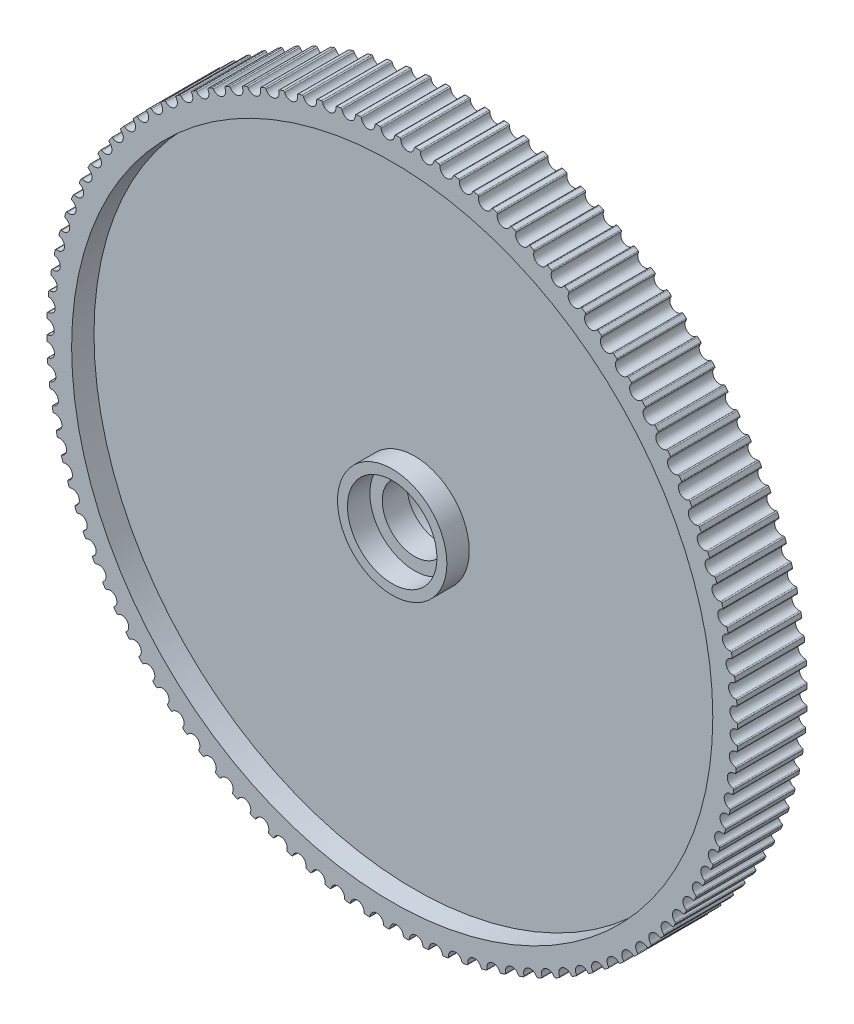
SolidWorks part; units mm, degrees
ref_plane "Front Plane" through (0, 0, 0) normal (0, 0, 1) x (1, 0, 0)
ref_plane "Top Plane" through (0, 0, 0) normal (0, 1, 0) x (1, 0, 0)
ref_plane "Right Plane" through (0, 0, 0) normal (1, 0, 0) x (0, 0, -1)
sketch "Sketch2" plane through (0, 0, 0) normal (0, 0, 1) x (1, 0, 0)
  circle A0 centre (0, 0) radius 35.03 construction
  arc A1 (-3.2113, 34.6013) -> (-3.0921, 34.5062) centre (-3.2012, 34.4918) cw
  arc A2 (-3.0921, 34.5062) -> (-1.738, 34.6009) centre (-2.418, 34.5956) ccw
  arc A3 (-1.738, 34.6009) -> (-1.6332, 34.7116) centre (-1.628, 34.6017) cw
  arc A4 (-1.6332, 34.7116) -> (-1.2307, 34.7282) centre (0, 0) cw
  circle A5 centre (0, 0) radius 34.75 construction
  circle A6 centre (0, 0) radius 34 construction
  arc A7 (0.3511, 34.7482) -> (0.7538, 34.7418) centre (0, 0) cw
  arc A8 (0.2401, 34.6437) -> (0.3511, 34.7482) centre (0.35, 34.6382) cw
  arc A9 (-1.1172, 34.6265) -> (0.2401, 34.6437) centre (-0.4391, 34.6772) ccw
  arc A10 (-1.2307, 34.7282) -> (-1.1172, 34.6265) centre (-1.2269, 34.6183) cw
  arc A11 (2.3343, 34.6715) -> (2.736, 34.6421) centre (0, 0) cw
  arc A12 (2.2175, 34.5735) -> (2.3343, 34.6715) centre (2.3269, 34.5618) cw
  arc A13 (0.8614, 34.6338) -> (2.2175, 34.5735) centre (1.5413, 34.6457) ccw
  arc A14 (0.7538, 34.7418) -> (0.8614, 34.6338) centre (0.7515, 34.6318) cw
  arc A15 (4.3098, 34.4817) -> (4.7092, 34.4294) centre (0, 0) cw
  arc A16 (4.1876, 34.3905) -> (4.3098, 34.4817) centre (4.2962, 34.3726) cw
  arc A17 (2.8372, 34.5281) -> (4.1876, 34.3905) centre (3.5167, 34.5012) ccw
  arc A18 (2.736, 34.6421) -> (2.8372, 34.5281) centre (2.7273, 34.5325) cw
  arc A19 (6.2713, 34.1794) -> (6.6671, 34.1044) centre (0, 0) cw
  arc A20 (6.1441, 34.0953) -> (6.2713, 34.1794) centre (6.2514, 34.0712) cw
  arc A21 (4.8038, 34.3098) -> (6.1441, 34.0953) centre (5.4806, 34.2442) ccw
  arc A22 (4.7092, 34.4294) -> (4.8038, 34.3098) centre (4.6943, 34.3204) cw
  arc A23 (8.2123, 33.7657) -> (8.6032, 33.6682) centre (0, 0) cw
  arc A24 (8.0806, 33.689) -> (8.2123, 33.7657) centre (8.1863, 33.6588) cw
  arc A25 (6.7547, 33.9796) -> (8.0806, 33.689) centre (7.4266, 33.8755) ccw
  arc A26 (6.6671, 34.1044) -> (6.7547, 33.9796) centre (6.646, 33.9965) cw
  arc A27 (10.1266, 33.2418) -> (10.5112, 33.1222) centre (0, 0) cw
  arc A28 (9.9906, 33.1727) -> (10.1266, 33.2418) centre (10.0945, 33.1365) cw
  arc A29 (8.6835, 33.5386) -> (9.9906, 33.1727) centre (9.3484, 33.3962) ccw
  arc A30 (8.6032, 33.6682) -> (8.6835, 33.5386) centre (8.5759, 33.5616) cw
  arc A31 (12.0078, 32.6094) -> (12.385, 32.4681) centre (0, 0) cw
  arc A32 (11.8681, 32.5482) -> (12.0078, 32.6094) centre (11.9698, 32.5062) cw
  arc A33 (10.584, 32.9882) -> (11.8681, 32.5482) centre (11.2397, 32.8081) ccw
  arc A34 (10.5112, 33.1222) -> (10.584, 32.9882) centre (10.4779, 33.0173) cw
  arc A35 (13.8498, 31.8707) -> (14.2183, 31.7081) centre (0, 0) cw
  arc A36 (13.7069, 31.8176) -> (13.8498, 31.8707) centre (13.806, 31.7699) cw
  arc A37 (12.45, 32.3301) -> (13.7069, 31.8176) centre (13.0944, 32.1129) ccw
  arc A38 (12.385, 32.4681) -> (12.45, 32.3301) centre (12.3458, 32.3653) cw
  arc A39 (15.6467, 31.0281) -> (16.0053, 30.8446) centre (0, 0) cw
  arc A40 (15.501, 30.9832) -> (15.6467, 31.0281) centre (15.5972, 30.9299) cw
  arc A41 (14.2754, 31.5667) -> (15.501, 30.9832) centre (14.9063, 31.313) ccw
  arc A42 (14.2183, 31.7081) -> (14.2754, 31.5667) centre (14.1733, 31.6077) cw
  arc A43 (17.3926, 30.0842) -> (17.7401, 29.8806) centre (0, 0) cw
  arc A44 (17.2445, 30.0478) -> (17.3926, 30.0842) centre (17.3375, 29.989) cw
  arc A45 (16.0542, 30.7002) -> (17.2445, 30.0478) centre (16.6696, 30.411) ccw
  arc A46 (16.0053, 30.8446) -> (16.0542, 30.7002) centre (15.9547, 30.747) cw
  arc A47 (19.0817, 29.0423) -> (19.417, 28.8191) centre (0, 0) cw
  arc A48 (18.9318, 29.0143) -> (19.0817, 29.0423) centre (19.0213, 28.9503) cw
  arc A49 (17.7807, 29.7336) -> (18.9318, 29.0143) centre (18.3786, 29.4097) ccw
  arc A50 (17.7401, 29.8806) -> (17.7807, 29.7336) centre (17.684, 29.786) cw
  arc A51 (20.7085, 27.9055) -> (21.0306, 27.6636) centre (0, 0) cw
  arc A52 (20.5573, 27.8862) -> (20.7085, 27.9055) centre (20.643, 27.8172) cw
  arc A53 (19.4491, 28.6701) -> (20.5573, 27.8862) centre (20.0276, 28.3125) ccw
  arc A54 (19.417, 28.8191) -> (19.4491, 28.6701) centre (19.3556, 28.7279) cw
  arc A55 (22.2679, 26.6778) -> (22.5756, 26.4179) centre (0, 0) cw
  arc A56 (22.1158, 26.6671) -> (22.2679, 26.6778) centre (22.1974, 26.5934) cw
  arc A57 (21.0542, 27.513) -> (22.1158, 26.6671) centre (21.6112, 27.123) ccw
  arc A58 (21.0306, 27.6636) -> (21.0542, 27.513) centre (20.964, 27.5761) cw
  arc A59 (23.7545, 25.363) -> (24.0469, 25.086) centre (0, 0) cw
  arc A60 (23.6021, 25.361) -> (23.7545, 25.363) centre (23.6793, 25.2828) cw
  arc A61 (22.5905, 26.2661) -> (23.6021, 25.361) centre (23.1244, 25.845) ccw
  arc A62 (22.5756, 26.4179) -> (22.5905, 26.2661) centre (22.5041, 26.3343) cw
  arc A63 (25.1637, 23.9656) -> (25.4399, 23.6723) centre (0, 0) cw
  arc A64 (25.0114, 23.9723) -> (25.1637, 23.9656) centre (25.0841, 23.8897) cw
  arc A65 (24.0532, 24.9336) -> (25.0114, 23.9723) centre (24.5621, 24.4827) ccw
  arc A66 (24.0469, 25.086) -> (24.0532, 24.9336) centre (23.9708, 25.0066) cw
  arc A67 (26.4909, 22.4899) -> (26.7498, 22.1813) centre (0, 0) cw
  arc A68 (26.3392, 22.5053) -> (26.4909, 22.4899) centre (26.407, 22.4187) cw
  arc A69 (25.4374, 23.5198) -> (26.3392, 22.5053) centre (25.9198, 23.0406) ccw
  arc A70 (25.4399, 23.6723) -> (25.4374, 23.5198) centre (25.3593, 23.5973) cw
  arc A71 (27.7316, 20.9409) -> (27.9725, 20.618) centre (0, 0) cw
  arc A72 (27.581, 20.9649) -> (27.7316, 20.9409) centre (27.6438, 20.8746) cw
  arc A73 (26.7386, 22.0293) -> (27.581, 20.9649) centre (27.1929, 21.5233) ccw
  arc A74 (26.7498, 22.1813) -> (26.7386, 22.0293) centre (26.6651, 22.1111) cw
  arc A75 (28.8819, 19.3236) -> (29.1039, 18.9875) centre (0, 0) cw
  arc A76 (28.7329, 19.3562) -> (28.8819, 19.3236) centre (28.7904, 19.2624) cw
  arc A77 (27.9526, 20.4669) -> (28.7329, 19.3562) centre (28.3772, 19.9358) ccw
  arc A78 (27.9725, 20.618) -> (27.9526, 20.4669) centre (27.8839, 20.5528) cw
  arc A79 (29.9379, 17.6432) -> (30.1404, 17.295) centre (0, 0) cw
  arc A80 (29.7911, 17.6843) -> (29.9379, 17.6432) centre (29.8431, 17.5874) cw
  arc A81 (29.0755, 18.8377) -> (29.7911, 17.6843) centre (29.4691, 18.2832) ccw
  arc A82 (29.1039, 18.9875) -> (29.0755, 18.8377) centre (29.0118, 18.9274) cw
  arc A83 (30.8963, 15.9053) -> (31.0786, 15.5461) centre (0, 0) cw
  arc A84 (30.752, 15.9547) -> (30.8963, 15.9053) centre (30.7985, 15.855) cw
  arc A85 (30.1035, 17.1471) -> (30.752, 15.9547) centre (30.4648, 16.571) ccw
  arc A86 (30.1404, 17.295) -> (30.1035, 17.1471) centre (30.045, 17.2403) cw
  arc A87 (31.7539, 14.1156) -> (31.9154, 13.7465) centre (0, 0) cw
  arc A88 (31.6127, 14.1731) -> (31.7539, 14.1156) centre (31.6534, 14.0709) cw
  arc A89 (31.0333, 15.4006) -> (31.6127, 14.1731) centre (31.3611, 14.8048) ccw
  arc A90 (31.0786, 15.5461) -> (31.0333, 15.4006) centre (30.9802, 15.4969) cw
  arc A91 (32.508, 12.2798) -> (32.6482, 11.9021) centre (0, 0) cw
  arc A92 (32.3703, 12.3452) -> (32.508, 12.2798) centre (32.4051, 12.2409) cw
  arc A93 (31.8619, 13.6038) -> (32.3703, 12.3452) centre (32.1552, 12.9903) ccw
  arc A94 (31.9154, 13.7465) -> (31.8619, 13.6038) centre (31.8144, 13.703) cw
  arc A95 (33.156, 10.4039) -> (33.2744, 10.0189) centre (0, 0) cw
  arc A96 (33.0223, 10.4771) -> (33.156, 10.4039) centre (33.0511, 10.371) cw
  arc A97 (32.5865, 11.7627) -> (33.0223, 10.4771) centre (32.8443, 11.1334) ccw
  arc A98 (32.6482, 11.9021) -> (32.5865, 11.7627) centre (32.5448, 11.8644) cw
  arc A99 (33.6959, 8.4941) -> (33.7921, 8.1029) centre (0, 0) cw
  arc A100 (33.5665, 8.5748) -> (33.6959, 8.4941) centre (33.5892, 8.4672) cw
  arc A101 (33.2049, 9.8831) -> (33.5665, 8.5748) centre (33.4263, 9.2402) ccw
  arc A102 (33.2744, 10.0189) -> (33.2049, 9.8831) centre (33.1691, 9.9871) cw
  arc A103 (34.1259, 6.5566) -> (34.1996, 6.1606) centre (0, 0) cw
  arc A104 (34.0013, 6.6446) -> (34.1259, 6.5566) centre (34.0178, 6.5358) cw
  arc A105 (33.7149, 7.9714) -> (34.0013, 6.6446) centre (33.8993, 7.3169) ccw
  arc A106 (33.7921, 8.1029) -> (33.7149, 7.9714) centre (33.6851, 8.0773) cw
  arc A107 (34.4445, 4.5977) -> (34.4955, 4.1981) centre (0, 0) cw
  arc A108 (34.3252, 4.6926) -> (34.4445, 4.5977) centre (34.3355, 4.5831) cw
  arc A109 (34.115, 6.0337) -> (34.3252, 4.6926) centre (34.2618, 5.3697) ccw
  arc A110 (34.1996, 6.1606) -> (34.115, 6.0337) centre (34.0913, 6.1411) cw
  arc A111 (34.6508, 2.6238) -> (34.6789, 2.2219) centre (0, 0) cw
  arc A112 (34.5371, 2.7254) -> (34.6508, 2.6238) centre (34.5411, 2.6155) cw
  arc A113 (34.4039, 4.0762) -> (34.5371, 2.7254) centre (34.5124, 3.4049) ccw
  arc A114 (34.4955, 4.1981) -> (34.4039, 4.0762) centre (34.3863, 4.1848) cw
  arc A115 (34.7441, 0.6413) -> (34.7492, 0.2385) centre (0, 0) cw
  arc A116 (34.6364, 0.7493) -> (34.7441, 0.6413) centre (34.6341, 0.6393) cw
  arc A117 (34.5805, 2.1055) -> (34.6364, 0.7493) centre (34.6505, 1.4291) ccw
  arc A118 (34.6789, 2.2219) -> (34.5805, 2.1055) centre (34.5691, 2.2149) cw
  arc A119 (34.724, -1.3432) -> (34.7061, -1.7456) centre (0, 0) cw
  arc A120 (34.6227, -1.2293) -> (34.724, -1.3432) centre (34.6141, -1.339) cw
  arc A121 (34.6443, 0.1279) -> (34.6227, -1.2293) centre (34.6756, -0.5514) ccw
  arc A122 (34.7492, 0.2385) -> (34.6443, 0.1279) centre (34.6392, 0.2378) cw
  arc A123 (34.5907, -3.3234) -> (34.5499, -3.7241) centre (0, 0) cw
  arc A124 (34.496, -3.2039) -> (34.5907, -3.3234) centre (34.4812, -3.3129) cw
  arc A125 (34.5951, -1.8501) -> (34.496, -3.2039) centre (34.5876, -2.5301) ccw
  arc A126 (34.7061, -1.7456) -> (34.5951, -1.8501) centre (34.5963, -1.7401) cw
  arc A127 (34.3446, -5.2927) -> (34.2809, -5.6905) centre (0, 0) cw
  arc A128 (34.2569, -5.168) -> (34.3446, -5.2927) centre (34.2359, -5.276) cw
  arc A129 (34.433, -3.8221) -> (34.2569, -5.168) centre (34.3867, -4.5005) ccw
  arc A130 (34.5499, -3.7241) -> (34.433, -3.8221) centre (34.4405, -3.7123) cw
  arc A131 (33.9864, -7.2448) -> (33.9001, -7.6382) centre (0, 0) cw
  arc A132 (33.906, -7.1152) -> (33.9864, -7.2448) centre (33.8788, -7.2218) cw
  arc A133 (34.1587, -5.7816) -> (33.906, -7.1152) centre (34.0737, -6.4563) ccw
  arc A134 (34.2809, -5.6905) -> (34.1587, -5.7816) centre (34.1724, -5.6724) cw
  arc A135 (33.5174, -9.1732) -> (33.4088, -9.5611) centre (0, 0) cw
  arc A136 (33.4445, -9.0393) -> (33.5174, -9.1732) centre (33.4113, -9.1442) cw
  arc A137 (33.7729, -7.7222) -> (33.4445, -9.0393) centre (33.6496, -8.391) ccw
  arc A138 (33.9001, -7.6382) -> (33.7729, -7.7222) centre (33.7928, -7.6141) cw
  arc A139 (32.939, -11.0717) -> (32.8085, -11.4528) centre (0, 0) cw
  arc A140 (32.8739, -10.9338) -> (32.939, -11.0717) centre (32.8348, -11.0367) cw
  arc A141 (33.277, -9.6377) -> (32.8739, -10.9338) centre (33.1157, -10.2983) ccw
  arc A142 (33.4088, -9.5611) -> (33.277, -9.6377) centre (33.303, -9.5308) cw
  arc A143 (32.2532, -12.9341) -> (32.1012, -13.3071) centre (0, 0) cw
  arc A144 (32.1961, -12.7927) -> (32.2532, -12.9341) centre (32.1511, -12.8932) cw
  arc A145 (32.6725, -11.5217) -> (32.1961, -12.7927) centre (32.4737, -12.172) ccw
  arc A146 (32.8085, -11.4528) -> (32.6725, -11.5217) centre (32.7046, -11.4165) cw
  arc A147 (31.4622, -14.7543) -> (31.2891, -15.118) centre (0, 0) cw
  arc A148 (31.4132, -14.6099) -> (31.4622, -14.7543) centre (31.3627, -14.7076) cw
  arc A149 (31.9614, -13.3682) -> (31.4132, -14.6099) centre (31.7259, -14.0061) ccw
  arc A150 (32.1012, -13.3071) -> (31.9614, -13.3682) centre (31.9995, -13.265) cw
  arc A151 (30.5686, -16.5264) -> (30.375, -16.8796) centre (0, 0) cw
  arc A152 (30.5279, -16.3794) -> (30.5686, -16.5264) centre (30.4719, -16.4741) cw
  arc A153 (31.1461, -15.171) -> (30.5279, -16.3794) centre (30.8746, -15.7944) ccw
  arc A154 (31.2891, -15.118) -> (31.1461, -15.171) centre (31.1901, -15.0701) cw
  arc A155 (29.5753, -18.2446) -> (29.3618, -18.5861) centre (0, 0) cw
  arc A156 (29.5431, -18.0955) -> (29.5753, -18.2446) centre (29.4817, -18.1868) cw
  arc A157 (30.2292, -16.9243) -> (29.5431, -18.0955) centre (29.9225, -17.5312) ccw
  arc A158 (30.375, -16.8796) -> (30.2292, -16.9243) centre (30.2789, -16.8262) cw
  arc A159 (28.4855, -19.9032) -> (28.2529, -20.2321) centre (0, 0) cw
  arc A160 (28.4618, -19.7526) -> (28.4855, -19.9032) centre (28.3953, -19.8402) cw
  arc A161 (29.2138, -18.6225) -> (28.4618, -19.7526) centre (28.8729, -19.2109) ccw
  arc A162 (29.3618, -18.5861) -> (29.2138, -18.6225) centre (29.2689, -18.5273) cw
  arc A163 (27.3028, -21.497) -> (27.0518, -21.812) centre (0, 0) cw
  arc A164 (27.2878, -21.3452) -> (27.3028, -21.497) centre (27.2164, -21.4289) cw
  arc A165 (28.103, -20.2599) -> (27.2878, -21.3452) centre (27.7291, -20.8279) ccw
  arc A166 (28.2529, -20.2321) -> (28.103, -20.2599) centre (28.1635, -20.168) cw
  arc A167 (26.031, -23.0206) -> (25.7625, -23.3208) centre (0, 0) cw
  arc A168 (26.0247, -22.8682) -> (26.031, -23.0206) centre (25.9486, -22.9477) cw
  arc A169 (26.9005, -21.8312) -> (26.0247, -22.8682) centre (26.4948, -22.3769) ccw
  arc A170 (27.0518, -21.812) -> (26.9005, -21.8312) centre (26.9662, -21.743) cw
  arc A171 (24.6744, -24.4691) -> (24.3891, -24.7535) centre (0, 0) cw
  arc A172 (24.6767, -24.3167) -> (24.6744, -24.4691) centre (24.5963, -24.3917) cw
  arc A173 (25.6103, -23.3313) -> (24.6767, -24.3167) centre (25.1741, -23.853) ccw
  arc A174 (25.7625, -23.3208) -> (25.6103, -23.3313) centre (25.6809, -23.247) cw
  arc A175 (23.2372, -25.8378) -> (22.9362, -26.1055) centre (0, 0) cw
  arc A176 (23.2483, -25.6858) -> (23.2372, -25.8378) centre (23.1637, -25.7561) cw
  arc A177 (24.2366, -24.7554) -> (23.2483, -25.6858) centre (23.7713, -25.2513) ccw
  arc A178 (24.3891, -24.7535) -> (24.2366, -24.7554) centre (24.3119, -24.6751) cw
  arc A179 (21.7243, -27.1223) -> (21.4084, -27.3723) centre (0, 0) cw
  arc A180 (21.744, -26.9711) -> (21.7243, -27.1223) centre (21.6555, -27.0364) cw
  arc A181 (22.7838, -26.0986) -> (21.744, -26.9711) centre (22.291, -26.5672) ccw
  arc A182 (22.9362, -26.1055) -> (22.7838, -26.0986) centre (22.8636, -26.0228) cw
  arc A183 (20.1405, -28.3183) -> (19.8109, -28.5498) centre (0, 0) cw
  arc A184 (20.1688, -28.1684) -> (20.1405, -28.3183) centre (20.0767, -28.2286) cw
  arc A185 (21.2567, -27.3568) -> (20.1688, -28.1684) centre (20.738, -27.7964) ccw
  arc A186 (21.4084, -27.3723) -> (21.2567, -27.3568) centre (21.3407, -27.2856) cw
  arc A187 (18.491, -29.4219) -> (18.1487, -29.6342) centre (0, 0) cw
  arc A188 (18.5278, -29.2739) -> (18.491, -29.4219) centre (18.4324, -29.3287) cw
  arc A189 (19.6603, -28.5257) -> (18.5278, -29.2739) centre (19.1173, -28.935) ccw
  arc A190 (19.8109, -28.5498) -> (19.6603, -28.5257) centre (19.7481, -28.4595) cw
  arc A191 (16.7811, -30.4295) -> (16.4273, -30.622) centre (0, 0) cw
  arc A192 (16.8263, -30.2839) -> (16.7811, -30.4295) centre (16.728, -30.3332) cw
  arc A193 (17.9997, -29.6015) -> (16.8263, -30.2839) centre (17.4342, -29.9792) ccw
  arc A194 (18.1487, -29.6342) -> (17.9997, -29.6015) centre (18.0912, -29.5404) cw
  arc A195 (15.0166, -31.3379) -> (14.6523, -31.5099) centre (0, 0) cw
  arc A196 (15.07, -31.1951) -> (15.0166, -31.3379) centre (14.969, -31.2387) cw
  arc A197 (16.2805, -30.5808) -> (15.07, -31.1951) centre (15.6943, -30.9256) ccw
  arc A198 (16.4273, -30.622) -> (16.2805, -30.5808) centre (16.3753, -30.5251) cw
  arc A199 (13.203, -32.1441) -> (12.8296, -32.295) centre (0, 0) cw
  arc A200 (13.2646, -32.0046) -> (13.203, -32.1441) centre (13.1613, -32.0423) cw
  arc A201 (14.5081, -31.4604) -> (13.2646, -32.0046) centre (13.9032, -31.7711) ccw
  arc A202 (14.6523, -31.5099) -> (14.5081, -31.4604) centre (14.6059, -31.4101) cw
  arc A203 (11.3464, -32.8454) -> (10.965, -32.9747) centre (0, 0) cw
  arc A204 (11.4158, -32.7096) -> (11.3464, -32.8454) centre (11.3105, -32.7414) cw
  arc A205 (12.6884, -32.2373) -> (11.4158, -32.7096) centre (12.0668, -32.513) ccw
  arc A206 (12.8296, -32.295) -> (12.6884, -32.2373) centre (12.789, -32.1927) cw
  arc A207 (9.4528, -33.4396) -> (9.0646, -33.5469) centre (0, 0) cw
  arc A208 (9.5299, -33.308) -> (9.4528, -33.4396) centre (9.4229, -33.3337) cw
  arc A209 (10.8273, -32.9091) -> (9.5299, -33.308) centre (10.191, -33.1489) ccw
  arc A210 (10.965, -32.9747) -> (10.8273, -32.9091) centre (10.9302, -32.8703) cw
  arc A211 (7.5284, -33.9247) -> (7.1347, -34.0097) centre (0, 0) cw
  arc A212 (7.6128, -33.7977) -> (7.5284, -33.9247) centre (7.5046, -33.8173) cw
  arc A213 (8.9309, -33.4736) -> (7.6128, -33.7977) centre (8.2819, -33.6766) ccw
  arc A214 (9.0646, -33.5469) -> (8.9309, -33.4736) centre (9.0359, -33.4407) cw
  arc A215 (5.5794, -34.2992) -> (5.1814, -34.3615) centre (0, 0) cw
  arc A216 (5.6709, -34.1772) -> (5.5794, -34.2992) centre (5.5617, -34.1906) cw
  arc A217 (7.0054, -33.9288) -> (5.6709, -34.1772) centre (6.3459, -34.0945) ccw
  arc A218 (7.1347, -34.0097) -> (7.0054, -33.9288) centre (7.1121, -33.902) cw
  arc A219 (3.6122, -34.5617) -> (3.2113, -34.6013) centre (0, 0) cw
  arc A220 (3.7105, -34.4452) -> (3.6122, -34.5617) centre (3.6008, -34.4523) cw
  arc A221 (5.057, -34.2734) -> (3.7105, -34.4452) centre (4.3891, -34.4011) ccw
  arc A222 (5.1814, -34.3615) -> (5.057, -34.2734) centre (5.165, -34.2528) cw
  arc A223 (1.6332, -34.7116) -> (1.2307, -34.7282) centre (0, 0) cw
  arc A224 (1.738, -34.6009) -> (1.6332, -34.7116) centre (1.628, -34.6017) cw
  arc A225 (3.0921, -34.5062) -> (1.738, -34.6009) centre (2.418, -34.5956) ccw
  arc A226 (3.2113, -34.6013) -> (3.0921, -34.5062) centre (3.2012, -34.4918) cw
  arc A227 (-0.3511, -34.7482) -> (-0.7538, -34.7418) centre (0, 0) cw
  arc A228 (-0.2401, -34.6437) -> (-0.3511, -34.7482) centre (-0.35, -34.6382) cw
  arc A229 (1.1172, -34.6265) -> (-0.2401, -34.6437) centre (0.4391, -34.6772) ccw
  arc A230 (1.2307, -34.7282) -> (1.1172, -34.6265) centre (1.2269, -34.6183) cw
  arc A231 (-2.3343, -34.6715) -> (-2.736, -34.6421) centre (0, 0) cw
  arc A232 (-2.2175, -34.5735) -> (-2.3343, -34.6715) centre (-2.3269, -34.5618) cw
  arc A233 (-0.8614, -34.6338) -> (-2.2175, -34.5735) centre (-1.5413, -34.6457) ccw
  arc A234 (-0.7538, -34.7418) -> (-0.8614, -34.6338) centre (-0.7515, -34.6318) cw
  arc A235 (-4.3098, -34.4817) -> (-4.7092, -34.4294) centre (0, 0) cw
  arc A236 (-4.1876, -34.3905) -> (-4.3098, -34.4817) centre (-4.2962, -34.3726) cw
  arc A237 (-2.8372, -34.5281) -> (-4.1876, -34.3905) centre (-3.5167, -34.5012) ccw
  arc A238 (-2.736, -34.6421) -> (-2.8372, -34.5281) centre (-2.7273, -34.5325) cw
  arc A239 (-6.2713, -34.1794) -> (-6.6671, -34.1044) centre (0, 0) cw
  arc A240 (-6.1441, -34.0953) -> (-6.2713, -34.1794) centre (-6.2514, -34.0712) cw
  arc A241 (-4.8038, -34.3098) -> (-6.1441, -34.0953) centre (-5.4806, -34.2442) ccw
  arc A242 (-4.7092, -34.4294) -> (-4.8038, -34.3098) centre (-4.6943, -34.3204) cw
  arc A243 (-8.2123, -33.7657) -> (-8.6032, -33.6682) centre (0, 0) cw
  arc A244 (-8.0806, -33.689) -> (-8.2123, -33.7657) centre (-8.1863, -33.6588) cw
  arc A245 (-6.7547, -33.9796) -> (-8.0806, -33.689) centre (-7.4266, -33.8755) ccw
  arc A246 (-6.6671, -34.1044) -> (-6.7547, -33.9796) centre (-6.646, -33.9965) cw
  arc A247 (-10.1266, -33.2418) -> (-10.5112, -33.1222) centre (0, 0) cw
  arc A248 (-9.9906, -33.1727) -> (-10.1266, -33.2418) centre (-10.0945, -33.1365) cw
  arc A249 (-8.6835, -33.5386) -> (-9.9906, -33.1727) centre (-9.3484, -33.3962) ccw
  arc A250 (-8.6032, -33.6682) -> (-8.6835, -33.5386) centre (-8.5759, -33.5616) cw
  arc A251 (-12.0078, -32.6094) -> (-12.385, -32.4681) centre (0, 0) cw
  arc A252 (-11.8681, -32.5482) -> (-12.0078, -32.6094) centre (-11.9698, -32.5062) cw
  arc A253 (-10.584, -32.9882) -> (-11.8681, -32.5482) centre (-11.2397, -32.8081) ccw
  arc A254 (-10.5112, -33.1222) -> (-10.584, -32.9882) centre (-10.4779, -33.0173) cw
  arc A255 (-13.8498, -31.8707) -> (-14.2183, -31.7081) centre (0, 0) cw
  arc A256 (-13.7069, -31.8176) -> (-13.8498, -31.8707) centre (-13.806, -31.7699) cw
  arc A257 (-12.45, -32.3301) -> (-13.7069, -31.8176) centre (-13.0944, -32.1129) ccw
  arc A258 (-12.385, -32.4681) -> (-12.45, -32.3301) centre (-12.3458, -32.3653) cw
  arc A259 (-15.6467, -31.0281) -> (-16.0053, -30.8446) centre (0, 0) cw
  arc A260 (-15.501, -30.9832) -> (-15.6467, -31.0281) centre (-15.5972, -30.9299) cw
  arc A261 (-14.2754, -31.5667) -> (-15.501, -30.9832) centre (-14.9063, -31.313) ccw
  arc A262 (-14.2183, -31.7081) -> (-14.2754, -31.5667) centre (-14.1733, -31.6077) cw
  arc A263 (-17.3926, -30.0842) -> (-17.7401, -29.8806) centre (0, 0) cw
  arc A264 (-17.2445, -30.0478) -> (-17.3926, -30.0842) centre (-17.3375, -29.989) cw
  arc A265 (-16.0542, -30.7002) -> (-17.2445, -30.0478) centre (-16.6696, -30.411) ccw
  arc A266 (-16.0053, -30.8446) -> (-16.0542, -30.7002) centre (-15.9547, -30.747) cw
  arc A267 (-19.0817, -29.0423) -> (-19.417, -28.8191) centre (0, 0) cw
  arc A268 (-18.9318, -29.0143) -> (-19.0817, -29.0423) centre (-19.0213, -28.9503) cw
  arc A269 (-17.7807, -29.7336) -> (-18.9318, -29.0143) centre (-18.3786, -29.4097) ccw
  arc A270 (-17.7401, -29.8806) -> (-17.7807, -29.7336) centre (-17.684, -29.786) cw
  arc A271 (-20.7085, -27.9055) -> (-21.0306, -27.6636) centre (0, 0) cw
  arc A272 (-20.5573, -27.8862) -> (-20.7085, -27.9055) centre (-20.643, -27.8172) cw
  arc A273 (-19.4491, -28.6701) -> (-20.5573, -27.8862) centre (-20.0276, -28.3125) ccw
  arc A274 (-19.417, -28.8191) -> (-19.4491, -28.6701) centre (-19.3556, -28.7279) cw
  arc A275 (-22.2679, -26.6778) -> (-22.5756, -26.4179) centre (0, 0) cw
  arc A276 (-22.1158, -26.6671) -> (-22.2679, -26.6778) centre (-22.1974, -26.5934) cw
  arc A277 (-21.0542, -27.513) -> (-22.1158, -26.6671) centre (-21.6112, -27.123) ccw
  arc A278 (-21.0306, -27.6636) -> (-21.0542, -27.513) centre (-20.964, -27.5761) cw
  arc A279 (-23.7545, -25.363) -> (-24.0469, -25.086) centre (0, 0) cw
  arc A280 (-23.6021, -25.361) -> (-23.7545, -25.363) centre (-23.6793, -25.2828) cw
  arc A281 (-22.5905, -26.2661) -> (-23.6021, -25.361) centre (-23.1244, -25.845) ccw
  arc A282 (-22.5756, -26.4179) -> (-22.5905, -26.2661) centre (-22.5041, -26.3343) cw
  arc A283 (-25.1637, -23.9656) -> (-25.4399, -23.6723) centre (0, 0) cw
  arc A284 (-25.0114, -23.9723) -> (-25.1637, -23.9656) centre (-25.0841, -23.8897) cw
  arc A285 (-24.0532, -24.9336) -> (-25.0114, -23.9723) centre (-24.5621, -24.4827) ccw
  arc A286 (-24.0469, -25.086) -> (-24.0532, -24.9336) centre (-23.9708, -25.0066) cw
  arc A287 (-26.4909, -22.4899) -> (-26.7498, -22.1813) centre (0, 0) cw
  arc A288 (-26.3392, -22.5053) -> (-26.4909, -22.4899) centre (-26.407, -22.4187) cw
  arc A289 (-25.4374, -23.5198) -> (-26.3392, -22.5053) centre (-25.9198, -23.0406) ccw
  arc A290 (-25.4399, -23.6723) -> (-25.4374, -23.5198) centre (-25.3593, -23.5973) cw
  arc A291 (-27.7316, -20.9409) -> (-27.9725, -20.618) centre (0, 0) cw
  arc A292 (-27.581, -20.9649) -> (-27.7316, -20.9409) centre (-27.6438, -20.8746) cw
  arc A293 (-26.7386, -22.0293) -> (-27.581, -20.9649) centre (-27.1929, -21.5233) ccw
  arc A294 (-26.7498, -22.1813) -> (-26.7386, -22.0293) centre (-26.6651, -22.1111) cw
  arc A295 (-28.8819, -19.3236) -> (-29.1039, -18.9875) centre (0, 0) cw
  arc A296 (-28.7329, -19.3562) -> (-28.8819, -19.3236) centre (-28.7904, -19.2624) cw
  arc A297 (-27.9526, -20.4669) -> (-28.7329, -19.3562) centre (-28.3772, -19.9358) ccw
  arc A298 (-27.9725, -20.618) -> (-27.9526, -20.4669) centre (-27.8839, -20.5528) cw
  arc A299 (-29.9379, -17.6432) -> (-30.1404, -17.295) centre (0, 0) cw
  arc A300 (-29.7911, -17.6843) -> (-29.9379, -17.6432) centre (-29.8431, -17.5874) cw
  arc A301 (-29.0755, -18.8377) -> (-29.7911, -17.6843) centre (-29.4691, -18.2832) ccw
  arc A302 (-29.1039, -18.9875) -> (-29.0755, -18.8377) centre (-29.0118, -18.9274) cw
  arc A303 (-30.8963, -15.9053) -> (-31.0786, -15.5461) centre (0, 0) cw
  arc A304 (-30.752, -15.9547) -> (-30.8963, -15.9053) centre (-30.7985, -15.855) cw
  arc A305 (-30.1035, -17.1471) -> (-30.752, -15.9547) centre (-30.4648, -16.571) ccw
  arc A306 (-30.1404, -17.295) -> (-30.1035, -17.1471) centre (-30.045, -17.2403) cw
  arc A307 (-31.7539, -14.1156) -> (-31.9154, -13.7465) centre (0, 0) cw
  arc A308 (-31.6127, -14.1731) -> (-31.7539, -14.1156) centre (-31.6534, -14.0709) cw
  arc A309 (-31.0333, -15.4006) -> (-31.6127, -14.1731) centre (-31.3611, -14.8048) ccw
  arc A310 (-31.0786, -15.5461) -> (-31.0333, -15.4006) centre (-30.9802, -15.4969) cw
  arc A311 (-32.508, -12.2798) -> (-32.6482, -11.9021) centre (0, 0) cw
  arc A312 (-32.3703, -12.3452) -> (-32.508, -12.2798) centre (-32.4051, -12.2409) cw
  arc A313 (-31.8619, -13.6038) -> (-32.3703, -12.3452) centre (-32.1552, -12.9903) ccw
  arc A314 (-31.9154, -13.7465) -> (-31.8619, -13.6038) centre (-31.8144, -13.703) cw
  arc A315 (-33.156, -10.4039) -> (-33.2744, -10.0189) centre (0, 0) cw
  arc A316 (-33.0223, -10.4771) -> (-33.156, -10.4039) centre (-33.0511, -10.371) cw
  arc A317 (-32.5865, -11.7627) -> (-33.0223, -10.4771) centre (-32.8443, -11.1334) ccw
  arc A318 (-32.6482, -11.9021) -> (-32.5865, -11.7627) centre (-32.5448, -11.8644) cw
  arc A319 (-33.6959, -8.4941) -> (-33.7921, -8.1029) centre (0, 0) cw
  arc A320 (-33.5665, -8.5748) -> (-33.6959, -8.4941) centre (-33.5892, -8.4672) cw
  arc A321 (-33.2049, -9.8831) -> (-33.5665, -8.5748) centre (-33.4263, -9.2402) ccw
  arc A322 (-33.2744, -10.0189) -> (-33.2049, -9.8831) centre (-33.1691, -9.9871) cw
  arc A323 (-34.1259, -6.5566) -> (-34.1996, -6.1606) centre (0, 0) cw
  arc A324 (-34.0013, -6.6446) -> (-34.1259, -6.5566) centre (-34.0178, -6.5358) cw
  arc A325 (-33.7149, -7.9714) -> (-34.0013, -6.6446) centre (-33.8993, -7.3169) ccw
  arc A326 (-33.7921, -8.1029) -> (-33.7149, -7.9714) centre (-33.6851, -8.0773) cw
  arc A327 (-34.4445, -4.5977) -> (-34.4955, -4.1981) centre (0, 0) cw
  arc A328 (-34.3252, -4.6926) -> (-34.4445, -4.5977) centre (-34.3355, -4.5831) cw
  arc A329 (-34.115, -6.0337) -> (-34.3252, -4.6926) centre (-34.2618, -5.3697) ccw
  arc A330 (-34.1996, -6.1606) -> (-34.115, -6.0337) centre (-34.0913, -6.1411) cw
  arc A331 (-34.6508, -2.6238) -> (-34.6789, -2.2219) centre (0, 0) cw
  arc A332 (-34.5371, -2.7254) -> (-34.6508, -2.6238) centre (-34.5411, -2.6155) cw
  arc A333 (-34.4039, -4.0762) -> (-34.5371, -2.7254) centre (-34.5124, -3.4049) ccw
  arc A334 (-34.4955, -4.1981) -> (-34.4039, -4.0762) centre (-34.3863, -4.1848) cw
  arc A335 (-34.7441, -0.6413) -> (-34.7492, -0.2385) centre (0, 0) cw
  arc A336 (-34.6364, -0.7493) -> (-34.7441, -0.6413) centre (-34.6341, -0.6393) cw
  arc A337 (-34.5805, -2.1055) -> (-34.6364, -0.7493) centre (-34.6505, -1.4291) ccw
  arc A338 (-34.6789, -2.2219) -> (-34.5805, -2.1055) centre (-34.5691, -2.2149) cw
  arc A339 (-34.724, 1.3432) -> (-34.7061, 1.7456) centre (0, 0) cw
  arc A340 (-34.6227, 1.2293) -> (-34.724, 1.3432) centre (-34.6141, 1.339) cw
  arc A341 (-34.6443, -0.1279) -> (-34.6227, 1.2293) centre (-34.6756, 0.5514) ccw
  arc A342 (-34.7492, -0.2385) -> (-34.6443, -0.1279) centre (-34.6392, -0.2378) cw
  arc A343 (-34.5907, 3.3234) -> (-34.5499, 3.7241) centre (0, 0) cw
  arc A344 (-34.496, 3.2039) -> (-34.5907, 3.3234) centre (-34.4812, 3.3129) cw
  arc A345 (-34.5951, 1.8501) -> (-34.496, 3.2039) centre (-34.5876, 2.5301) ccw
  arc A346 (-34.7061, 1.7456) -> (-34.5951, 1.8501) centre (-34.5963, 1.7401) cw
  arc A347 (-34.3446, 5.2927) -> (-34.2809, 5.6905) centre (0, 0) cw
  arc A348 (-34.2569, 5.168) -> (-34.3446, 5.2927) centre (-34.2359, 5.276) cw
  arc A349 (-34.433, 3.8221) -> (-34.2569, 5.168) centre (-34.3867, 4.5005) ccw
  arc A350 (-34.5499, 3.7241) -> (-34.433, 3.8221) centre (-34.4405, 3.7123) cw
  arc A351 (-33.9864, 7.2448) -> (-33.9001, 7.6382) centre (0, 0) cw
  arc A352 (-33.906, 7.1152) -> (-33.9864, 7.2448) centre (-33.8788, 7.2218) cw
  arc A353 (-34.1587, 5.7816) -> (-33.906, 7.1152) centre (-34.0737, 6.4563) ccw
  arc A354 (-34.2809, 5.6905) -> (-34.1587, 5.7816) centre (-34.1724, 5.6724) cw
  arc A355 (-33.5174, 9.1732) -> (-33.4088, 9.5611) centre (0, 0) cw
  arc A356 (-33.4445, 9.0393) -> (-33.5174, 9.1732) centre (-33.4113, 9.1442) cw
  arc A357 (-33.7729, 7.7222) -> (-33.4445, 9.0393) centre (-33.6496, 8.391) ccw
  arc A358 (-33.9001, 7.6382) -> (-33.7729, 7.7222) centre (-33.7928, 7.6141) cw
  arc A359 (-32.939, 11.0717) -> (-32.8085, 11.4528) centre (0, 0) cw
  arc A360 (-32.8739, 10.9338) -> (-32.939, 11.0717) centre (-32.8348, 11.0367) cw
  arc A361 (-33.277, 9.6377) -> (-32.8739, 10.9338) centre (-33.1157, 10.2983) ccw
  arc A362 (-33.4088, 9.5611) -> (-33.277, 9.6377) centre (-33.303, 9.5308) cw
  arc A363 (-32.2532, 12.9341) -> (-32.1012, 13.3071) centre (0, 0) cw
  arc A364 (-32.1961, 12.7927) -> (-32.2532, 12.9341) centre (-32.1511, 12.8932) cw
  arc A365 (-32.6725, 11.5217) -> (-32.1961, 12.7927) centre (-32.4737, 12.172) ccw
  arc A366 (-32.8085, 11.4528) -> (-32.6725, 11.5217) centre (-32.7046, 11.4165) cw
  arc A367 (-31.4622, 14.7543) -> (-31.2891, 15.118) centre (0, 0) cw
  arc A368 (-31.4132, 14.6099) -> (-31.4622, 14.7543) centre (-31.3627, 14.7076) cw
  arc A369 (-31.9614, 13.3682) -> (-31.4132, 14.6099) centre (-31.7259, 14.0061) ccw
  arc A370 (-32.1012, 13.3071) -> (-31.9614, 13.3682) centre (-31.9995, 13.265) cw
  arc A371 (-30.5686, 16.5264) -> (-30.375, 16.8796) centre (0, 0) cw
  arc A372 (-30.5279, 16.3794) -> (-30.5686, 16.5264) centre (-30.4719, 16.4741) cw
  arc A373 (-31.1461, 15.171) -> (-30.5279, 16.3794) centre (-30.8746, 15.7944) ccw
  arc A374 (-31.2891, 15.118) -> (-31.1461, 15.171) centre (-31.1901, 15.0701) cw
  arc A375 (-29.5753, 18.2446) -> (-29.3618, 18.5861) centre (0, 0) cw
  arc A376 (-29.5431, 18.0955) -> (-29.5753, 18.2446) centre (-29.4817, 18.1868) cw
  arc A377 (-30.2292, 16.9243) -> (-29.5431, 18.0955) centre (-29.9225, 17.5312) ccw
  arc A378 (-30.375, 16.8796) -> (-30.2292, 16.9243) centre (-30.2789, 16.8262) cw
  arc A379 (-28.4855, 19.9032) -> (-28.2529, 20.2321) centre (0, 0) cw
  arc A380 (-28.4618, 19.7526) -> (-28.4855, 19.9032) centre (-28.3953, 19.8402) cw
  arc A381 (-29.2138, 18.6225) -> (-28.4618, 19.7526) centre (-28.8729, 19.2109) ccw
  arc A382 (-29.3618, 18.5861) -> (-29.2138, 18.6225) centre (-29.2689, 18.5273) cw
  arc A383 (-27.3028, 21.497) -> (-27.0518, 21.812) centre (0, 0) cw
  arc A384 (-27.2878, 21.3452) -> (-27.3028, 21.497) centre (-27.2164, 21.4289) cw
  arc A385 (-28.103, 20.2599) -> (-27.2878, 21.3452) centre (-27.7291, 20.8279) ccw
  arc A386 (-28.2529, 20.2321) -> (-28.103, 20.2599) centre (-28.1635, 20.168) cw
  arc A387 (-26.031, 23.0206) -> (-25.7625, 23.3208) centre (0, 0) cw
  arc A388 (-26.0247, 22.8682) -> (-26.031, 23.0206) centre (-25.9486, 22.9477) cw
  arc A389 (-26.9005, 21.8312) -> (-26.0247, 22.8682) centre (-26.4948, 22.3769) ccw
  arc A390 (-27.0518, 21.812) -> (-26.9005, 21.8312) centre (-26.9662, 21.743) cw
  arc A391 (-24.6744, 24.4691) -> (-24.3891, 24.7535) centre (0, 0) cw
  arc A392 (-24.6767, 24.3167) -> (-24.6744, 24.4691) centre (-24.5963, 24.3917) cw
  arc A393 (-25.6103, 23.3313) -> (-24.6767, 24.3167) centre (-25.1741, 23.853) ccw
  arc A394 (-25.7625, 23.3208) -> (-25.6103, 23.3313) centre (-25.6809, 23.247) cw
  arc A395 (-23.2372, 25.8378) -> (-22.9362, 26.1055) centre (0, 0) cw
  arc A396 (-23.2483, 25.6858) -> (-23.2372, 25.8378) centre (-23.1637, 25.7561) cw
  arc A397 (-24.2366, 24.7554) -> (-23.2483, 25.6858) centre (-23.7713, 25.2513) ccw
  arc A398 (-24.3891, 24.7535) -> (-24.2366, 24.7554) centre (-24.3119, 24.6751) cw
  arc A399 (-21.7243, 27.1223) -> (-21.4084, 27.3723) centre (0, 0) cw
  arc A400 (-21.744, 26.9711) -> (-21.7243, 27.1223) centre (-21.6555, 27.0364) cw
  arc A401 (-22.7838, 26.0986) -> (-21.744, 26.9711) centre (-22.291, 26.5672) ccw
  arc A402 (-22.9362, 26.1055) -> (-22.7838, 26.0986) centre (-22.8636, 26.0228) cw
  arc A403 (-20.1405, 28.3183) -> (-19.8109, 28.5498) centre (0, 0) cw
  arc A404 (-20.1688, 28.1684) -> (-20.1405, 28.3183) centre (-20.0767, 28.2286) cw
  arc A405 (-21.2567, 27.3568) -> (-20.1688, 28.1684) centre (-20.738, 27.7964) ccw
  arc A406 (-21.4084, 27.3723) -> (-21.2567, 27.3568) centre (-21.3407, 27.2856) cw
  arc A407 (-18.491, 29.4219) -> (-18.1487, 29.6342) centre (0, 0) cw
  arc A408 (-18.5278, 29.2739) -> (-18.491, 29.4219) centre (-18.4324, 29.3287) cw
  arc A409 (-19.6603, 28.5257) -> (-18.5278, 29.2739) centre (-19.1173, 28.935) ccw
  arc A410 (-19.8109, 28.5498) -> (-19.6603, 28.5257) centre (-19.7481, 28.4595) cw
  arc A411 (-16.7811, 30.4295) -> (-16.4273, 30.622) centre (0, 0) cw
  arc A412 (-16.8263, 30.2839) -> (-16.7811, 30.4295) centre (-16.728, 30.3332) cw
  arc A413 (-17.9997, 29.6015) -> (-16.8263, 30.2839) centre (-17.4342, 29.9792) ccw
  arc A414 (-18.1487, 29.6342) -> (-17.9997, 29.6015) centre (-18.0912, 29.5404) cw
  arc A415 (-15.0166, 31.3379) -> (-14.6523, 31.5099) centre (0, 0) cw
  arc A416 (-15.07, 31.1951) -> (-15.0166, 31.3379) centre (-14.969, 31.2387) cw
  arc A417 (-16.2805, 30.5808) -> (-15.07, 31.1951) centre (-15.6943, 30.9256) ccw
  arc A418 (-16.4273, 30.622) -> (-16.2805, 30.5808) centre (-16.3753, 30.5251) cw
  arc A419 (-13.203, 32.1441) -> (-12.8296, 32.295) centre (0, 0) cw
  arc A420 (-13.2646, 32.0046) -> (-13.203, 32.1441) centre (-13.1613, 32.0423) cw
  arc A421 (-14.5081, 31.4604) -> (-13.2646, 32.0046) centre (-13.9032, 31.7711) ccw
  arc A422 (-14.6523, 31.5099) -> (-14.5081, 31.4604) centre (-14.6059, 31.4101) cw
  arc A423 (-11.3464, 32.8454) -> (-10.965, 32.9747) centre (0, 0) cw
  arc A424 (-11.4158, 32.7096) -> (-11.3464, 32.8454) centre (-11.3105, 32.7414) cw
  arc A425 (-12.6884, 32.2373) -> (-11.4158, 32.7096) centre (-12.0668, 32.513) ccw
  arc A426 (-12.8296, 32.295) -> (-12.6884, 32.2373) centre (-12.789, 32.1927) cw
  arc A427 (-9.4528, 33.4396) -> (-9.0646, 33.5469) centre (0, 0) cw
  arc A428 (-9.5299, 33.308) -> (-9.4528, 33.4396) centre (-9.4229, 33.3337) cw
  arc A429 (-10.8273, 32.9091) -> (-9.5299, 33.308) centre (-10.191, 33.1489) ccw
  arc A430 (-10.965, 32.9747) -> (-10.8273, 32.9091) centre (-10.9302, 32.8703) cw
  arc A431 (-7.5284, 33.9247) -> (-7.1347, 34.0097) centre (0, 0) cw
  arc A432 (-7.6128, 33.7977) -> (-7.5284, 33.9247) centre (-7.5046, 33.8173) cw
  arc A433 (-8.9309, 33.4736) -> (-7.6128, 33.7977) centre (-8.2819, 33.6766) ccw
  arc A434 (-9.0646, 33.5469) -> (-8.9309, 33.4736) centre (-9.0359, 33.4407) cw
  arc A435 (-5.5794, 34.2992) -> (-5.1814, 34.3615) centre (0, 0) cw
  arc A436 (-5.6709, 34.1772) -> (-5.5794, 34.2992) centre (-5.5617, 34.1906) cw
  arc A437 (-7.0054, 33.9288) -> (-5.6709, 34.1772) centre (-6.3459, 34.0945) ccw
  arc A438 (-7.1347, 34.0097) -> (-7.0054, 33.9288) centre (-7.1121, 33.902) cw
  arc A439 (-3.6122, 34.5617) -> (-3.2113, 34.6013) centre (0, 0) cw
  arc A440 (-3.7105, 34.4452) -> (-3.6122, 34.5617) centre (-3.6008, 34.4523) cw
  arc A441 (-5.057, 34.2734) -> (-3.7105, 34.4452) centre (-4.3891, 34.4011) ccw
  arc A442 (-5.1814, 34.3615) -> (-5.057, 34.2734) centre (-5.165, 34.2528) cw
  point P889 (0, 0)
  dimension "D1" = 70.06
  dimension "D2" = 0.11
  dimension "D3" = 0.68
  dimension "D4" = 69.5
  dimension "D5" = 68
  dimension "D6" = 110
extrude "Boss-Extrude1" add sketch "Sketch2" along normal mid plane 7
sketch "Sketch4" plane through (0, 0, 0) normal (0, 0, 1) x (1, 0, 0)
  circle A0 centre (0, 0) radius 32.25
  dimension "D1" = 64.5
extrude "Cut-Extrude2" cut sketch "Sketch4" against normal mid plane 7
sketch "Sketch5" plane through (0, 0, 3.5) normal (0, 0, 1) x (1, 0, 0)
  circle A0 centre (0, 0) radius 32.25
  circle A1 centre (0, 0) radius 36
  dimension "D1" = 72
sketch "Sketch6" plane through (0, 0, 0) normal (0, 0, 1) x (1, 0, 0)
  circle A0 centre (0, 0) radius 3.25
  circle A1 centre (0, 0) radius 4.5
  circle A2 centre (0, 0) radius 5.5
  circle A3 centre (0, 0) radius 32.25
  dimension "D1" = 6.5
  dimension "D2" = 9
  dimension "D3" = 11
extrude "Boss-Extrude2" add sketch "Sketch6" along normal mid plane 2.5 contours A3 A2 | A1 A0 region at (-4.3727, 0, 0) region at (-31.3378, 0, 0)
extrude "Boss-Extrude3" add sketch "Sketch6<3>" along normal mid plane 7 contours A2 A1 region at (-5.3444, 0, 0)
sketch "Sketch6<3>" plane through (0, 0, 0) normal (0, 0, 1) x (1, 0, 0) same geometry as "Sketch6"
